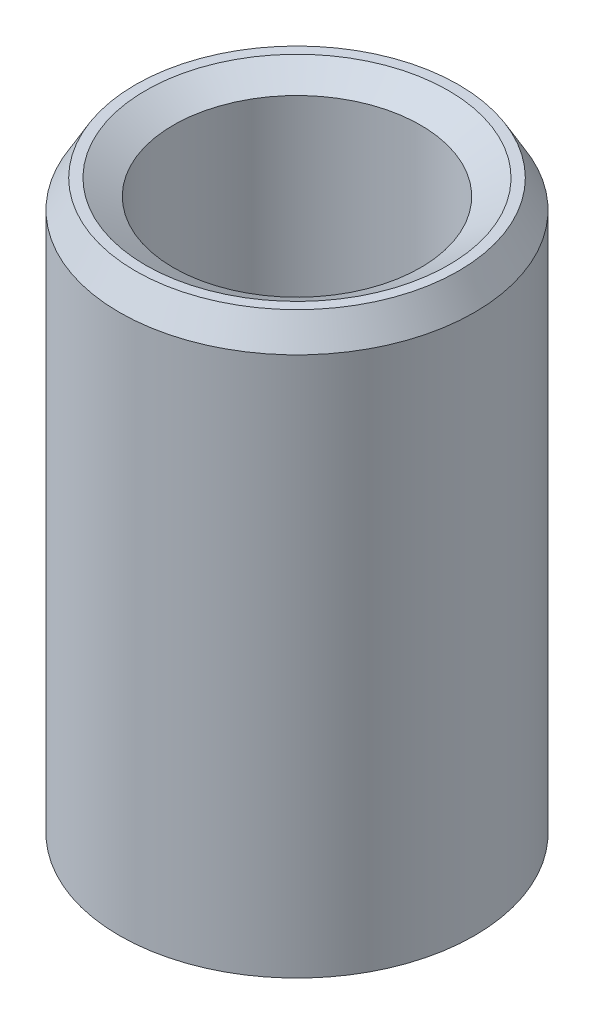
SolidWorks part; units mm, degrees
ref_plane "Front Plane" through (0, 0, 0) normal (0, 0, 1) x (1, 0, 0)
ref_plane "Top Plane" through (0, 0, 0) normal (0, 1, 0) x (1, 0, 0)
ref_plane "Right Plane" through (0, 0, 0) normal (1, 0, 0) x (0, 0, -1)
sketch "Sketch1" plane through (0, 0, 0) normal (0, 1, 0) x (1, 0, 0)
  circle A0 centre (0, 0) radius 25
  dimension "SLEEVE_OD" = 50
extrude "Boss-Extrude1" add sketch "Sketch1" along normal blind 82.1864
sketch "Sketch2" plane through (0, 0, 0) normal (0, 1, 0) x (1, 0, 0)
  circle A0 centre (0, 0) radius 17.4015
  dimension "BORE_D" = 34.8029
extrude "Cut-Extrude1" cut sketch "Sketch2" along normal through all
chamfer "Chamfer1" distance 3.9157 angle 30 4 edges at (0, 82.1864, 17.4015) (0, 0, 17.4015) (0, 0, 25) (0, 82.1864, 25) first distance on face at (0, 82.1864, 17.4015) first distance on face at (0, 0, 17.4015) first distance on face at (0, 82.1864, 25)
